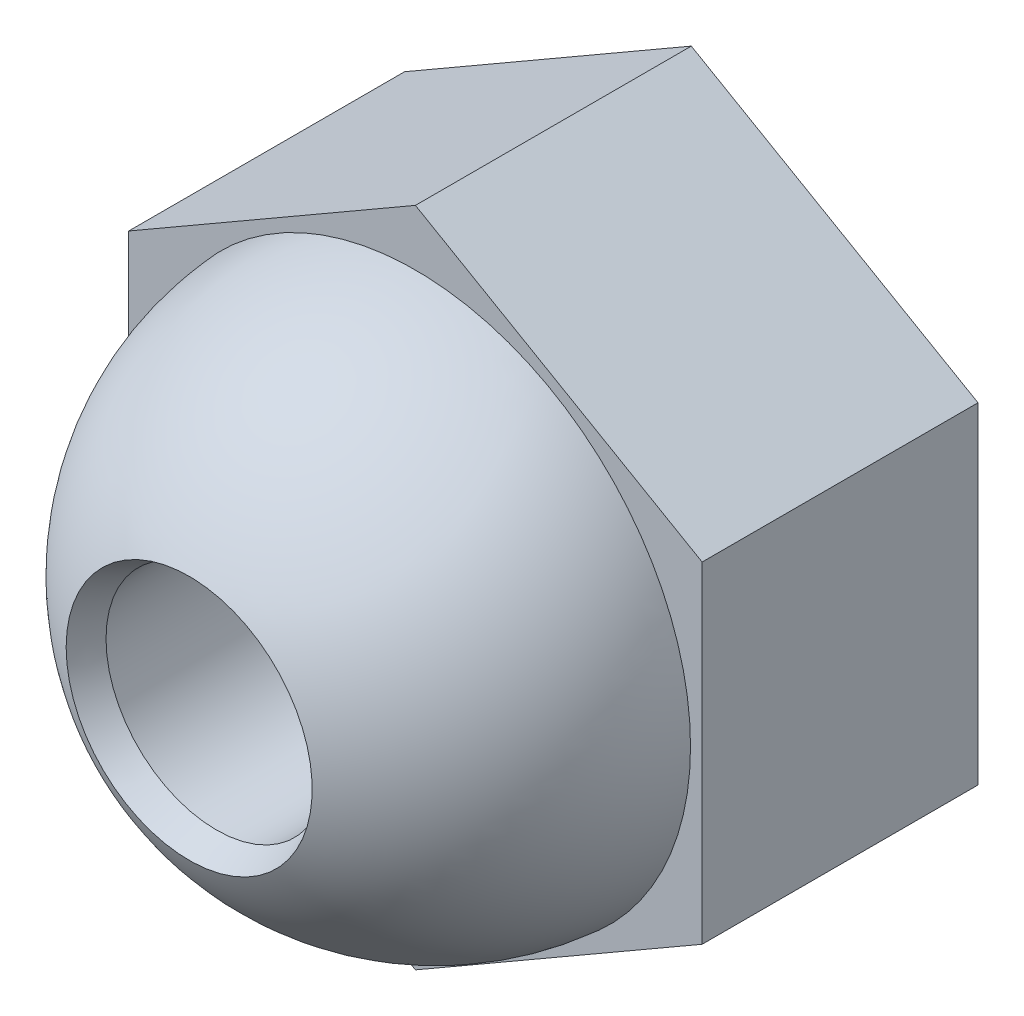
SolidWorks part; units mm, degrees
ref_plane "Front Plane" through (0, 0, 0) normal (0, 0, 1) x (1, 0, 0)
ref_plane "Top Plane" through (0, 0, 0) normal (0, 1, 0) x (1, 0, 0)
ref_plane "Right Plane" through (0, 0, 0) normal (1, 0, 0) x (0, 0, -1)
sketch "Sketch1" plane through (0, 0, 0) normal (0, 0, 1) x (1, 0, 0)
  line L1 (0, 12) -> (-10.3923, 6)
  line L2 (-10.3923, 6) -> (-10.3923, -6)
  line L3 (-10.3923, -6) -> (0, -12)
  line L4 (0, -12) -> (10.3923, -6)
  line L5 (10.3923, -6) -> (10.3923, 6)
  line L6 (10.3923, 6) -> (0, 12)
  circle A0 centre (0, 0) radius 8
  circle A1 centre (0, 0) radius 10.3923 construction
  point P3 (0, 0)
  point P11 (0, 12)
  dimension "D1" = 16
  dimension "D2" = 12
extrude "Boss-Extrude1" add sketch "Sketch1" along normal blind 10
sketch "Sketch4" plane through (0, 0, 0) normal (0, 1, 0) x (1, 0, 0)
  line L0 (0, -10) -> (0, -18.5225) construction
  line L1 (0, -10) -> (0, 0) construction
  line L2 (0, -10) -> (-10.3923, -10) construction
  line L3 (-9.9719, -10) -> (-4, -10)
  line L4 (-4, -10) -> (-4, -18.416)
  arc A0 (-9.9719, -10) -> (-4, -18.416) centre (0, -9.2508) ccw
  dimension "D2" = 10
  dimension "D3" = 4
revolve "Revolve3" add sketch "Sketch4" angle 360 about L0
sketch "Sketch6" plane through (0, 0, 0) normal (0, 0, -1) x (-1, 0, 0)
  circle A0 centre (0, 0) radius 8
curve "Helix/Spiral1" pitch 1.5 height 10 radius 8 centre (0, 0, 0) axis (0, 0, 1) start towards (-1, 0, 0)
sketch "Sketch7" plane through (0, 0, 0) normal (0, 1, 0) x (1, 0, 0)
  line L0 (7.9974, -0.756) -> (8.5336, -0.756) construction
  line L1 (7.9974, -0.256) -> (7.9974, -1.256)
  line L2 (7.9974, -1.256) -> (8.5336, -1.006)
  line L3 (8.5336, -1.006) -> (8.5336, -0.506)
  line L4 (7.9974, -0.256) -> (8.5336, -0.506)
  spline S0 degree 3 poles (-8, 0) (-8, -0.0312) (-7.5781, -0.0944) (-5.7773, -0.1887) (-3.0859, -0.283) (0.0811, -0.3774) (3.2356, -0.4717) (5.8914, -0.566) (7.6391, -0.6604) (8.2093, -0.7547) (7.5142, -0.8491) (5.6609, -0.9434) (2.935, -1.0377) (-0.2433, -1.1321) (-3.3841, -1.2264) (-6.0033, -1.3208) (-7.6971, -1.4151) (-8.2045, -1.5094) (-7.4473, -1.6038) (-5.5422, -1.6981) (-2.7829, -1.7925) (0.4054, -1.8868) (3.5312, -1.9811) (6.1128, -2.0755) (7.7521, -2.1698) (8.1965, -2.2642) (7.3776, -2.3585) (5.4215, -2.4528) (2.6297, -2.5472) (-0.5674, -2.6415) (-3.677, -2.7358) (-6.2199, -2.8302) (-7.804, -2.9245) (-8.1853, -3.0189) (-7.3049, -3.1132) (-5.2986, -3.2075) (-2.4755, -3.3019) (0.7291, -3.3962) (3.8213, -3.4906) (6.3246, -3.5849) (7.8529, -3.6792) (8.1709, -3.7736) (7.2294, -3.8679) (5.1736, -3.9623) (2.3204, -4.0566) (-0.8905, -4.1509) (-3.9642, -4.2453) (-6.4268, -4.3396) (-7.8988, -4.434) (-8.1533, -4.5283) (-7.1511, -4.6226) (-5.0466, -4.717) (-2.1643, -4.8113) (1.0516, -4.9057) (4.1055, -5) (6.5265, -5.0943) (7.9416, -5.1887) (8.1325, -5.283) (7.07, -5.3774) (4.9177, -5.4717) (2.0074, -5.566) (-1.2123, -5.6604) (-4.2452, -5.7547) (-6.6237, -5.8491) (-7.9812, -5.9434) (-8.1086, -6.0377) (-6.9861, -6.1321) (-4.7868, -6.2264) (-1.8497, -6.3208) (1.3725, -6.4151) (4.3832, -6.5094) (6.7182, -6.6038) (8.0178, -6.6981) (8.0815, -6.7925) (6.8995, -6.8868) (4.6541, -6.9811) (1.6913, -7.0755) (-1.5322, -7.1698) (-4.5195, -7.2642) (-6.8102, -7.3585) (-8.0512, -7.4528) (-8.0512, -7.5472) (-6.8102, -7.6415) (-4.5195, -7.7358) (-1.5322, -7.8302) (1.6913, -7.9245) (4.6541, -8.0189) (6.8995, -8.1132) (8.0815, -8.2075) (8.0178, -8.3019) (6.7182, -8.3962) (4.3832, -8.4906) (1.3725, -8.5849) (-1.8497, -8.6792) (-4.7868, -8.7736) (-6.9861, -8.8679) (-8.1086, -8.9623) (-7.9812, -9.0566) (-6.6237, -9.1509) (-4.2452, -9.2453) (-1.2123, -9.3396) (2.0074, -9.434) (4.9177, -9.5283) (7.0699, -9.6226) (8.1327, -9.717) (7.9408, -9.8113) (6.5292, -9.9056) (4.9067, -9.9688) (4, -10) knots 0 0 0 0 0.009434 0.018868 0.028302 0.037736 0.04717 0.056604 0.066038 0.075472 0.084906 0.09434 0.103774 0.113208 0.122642 0.132075 0.141509 0.150943 0.160377 0.169811 0.179245 0.188679 0.198113 0.207547 0.216981 0.226415 0.235849 0.245283 0.254717 0.264151 0.273585 0.283019 0.292453 0.301887 0.311321 0.320755 0.330189 0.339623 0.349057 0.358491 0.367925 0.377358 0.386792 0.396226 0.40566 0.415094 0.424528 0.433962 0.443396 0.45283 0.462264 0.471698 0.481132 0.490566 0.5 0.509434 0.518868 0.528302 0.537736 0.54717 0.556604 0.566038 0.575472 0.584906 0.59434 0.603774 0.613208 0.622642 0.632075 0.641509 0.650943 0.660377 0.669811 0.679245 0.688679 0.698113 0.707547 0.716981 0.726415 0.735849 0.745283 0.754717 0.764151 0.773585 0.783019 0.792453 0.801887 0.811321 0.820755 0.830189 0.839623 0.849057 0.858491 0.867925 0.877358 0.886792 0.896226 0.90566 0.915094 0.924528 0.933962 0.943396 0.95283 0.962264 0.971698 0.981132 0.990566 1 1 1 1 construction
  dimension "D1" = 0.25
  dimension "D2" = 0.5
  dimension "D3" = 65
sweep "Cut-Sweep1" cut profiles "Sketch7" path "Helix/Spiral1" align with end faces yes
chamfer "Chamfer1" distance 1.2 angle 25 1 edges at (-4, 0, 18.416) first distance on face at (-4, 0, 10)
